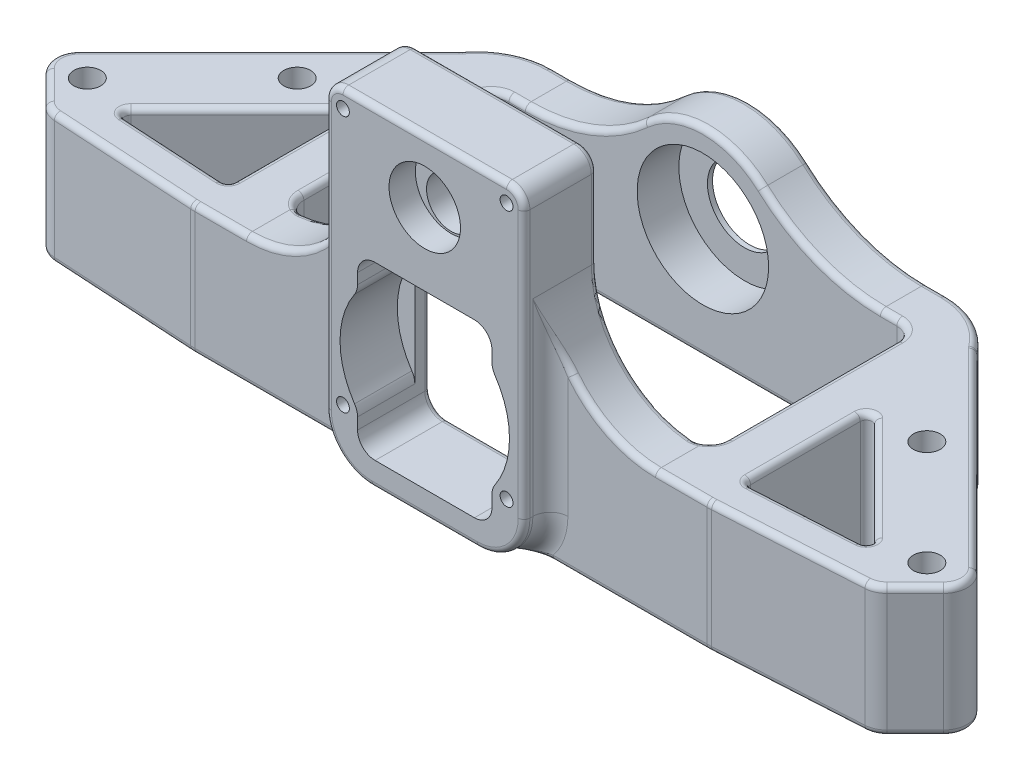
SolidWorks part; units mm, degrees
ref_plane "Front Plane" through (0, 0, 0) normal (0, 0, 1) x (1, 0, 0)
ref_plane "Top Plane" through (0, 0, 0) normal (0, 1, 0) x (1, 0, 0)
ref_plane "Right Plane" through (0, 0, 0) normal (1, 0, 0) x (0, 0, -1)
sketch "Sketch1" plane through (0, 0, 0) normal (0, 1, 0) x (1, 0, 0)
  line L0 (-44.195, -25.55) -> (-44.195, 25.55)
  line L1 (36.195, -17.55) -> (-36.195, -17.55)
  line L2 (36.195, -17.55) -> (36.195, 17.55)
  line L3 (36.195, 17.55) -> (-36.195, 17.55)
  line L4 (-36.195, -17.55) -> (-36.195, 17.55)
  line L5 (36.195, -17.55) -> (-36.195, 17.55) construction
  line L6 (36.195, 17.55) -> (-36.195, -17.55) construction
  line L11 (44.195, 25.55) -> (-44.195, 25.55)
  line L12 (44.195, -25.55) -> (44.195, 25.55)
  line L13 (44.195, -25.55) -> (-44.195, -25.55)
  line L14 (-79.6522, -15.223) -> (-70.8875, -23.9877)
  line L15 (-70.8875, -23.9877) -> (-44.195, 2.7047)
  line L16 (-79.6522, -15.223) -> (-44.195, 20.2342)
  line L17 (0, 0) -> (0, 65.6417) construction
  line L18 (-75.3776, -19.4976) -> (0, 55.88) construction
  line L19 (-44.195, -25.55) -> (-70.8875, -23.9877)
  line L20 (-44.195, -19.5397) -> (-65.2095, -18.3098)
  line L21 (44.195, -25.55) -> (70.8875, -23.9877)
  line L22 (44.195, -19.5397) -> (65.2095, -18.3098)
  line L23 (79.6522, -15.223) -> (44.195, 20.2342)
  line L24 (79.6522, -15.223) -> (70.8875, -23.9877)
  line L25 (70.8875, -23.9877) -> (44.195, 2.7047)
  line L26 (-75.3776, -19.4976) -> (-269.4077, -213.5277) construction
  circle A0 centre (-71.842, -15.962) radius 2.3
  circle A1 centre (-53.8815, 1.9985) radius 2.3
  circle A4 centre (53.8815, 1.9985) radius 2.3
  circle A5 centre (71.842, -15.962) radius 2.3
  point P0 (0, 0)
  point P21 (-75.3776, -19.4976)
  point P32 (-197.5656, -141.6856)
  point P34 (-215.5261, -159.6461)
  point P38 (0, 0)
  point P39 (0, 0)
  dimension "D10" = 4.6
  dimension "D1" = 8
  dimension "D2" = 45
  dimension "D3" = 55.88
  dimension "D4" = 5
  dimension "D5" = 76.2
  dimension "D6" = 12.3952
  dimension "D7" = 25.4
  dimension "D8" = 72.39
  dimension "D9" = 35.1
  dimension "D11" = 6
  dimension "D12" = 381
  dimension "D13" = 101.6
  dimension "D14" = 177.8
  dimension "D15" = 25.4
  dimension "D16" = 228.6
  dimension "D17" = 6.35
extrude "Boss-Extrude1" add sketch "Sketch1" along normal blind 22.25 contours L13 L12 L11 L0 L1 L4 L3 L2 | L0 L20 L15 L19 | L21 L25 L22 L12 | L25 L24 L23 L12 A4 A5 | L16 L14 L15 L0 A1 A0 region at (-56.1781, 0, 21.9627) region at (-43.174, 0, 22.5449) region at (56.1781, 0, 21.9627) region at (-59.6388, 0, 3.5495) region at (59.6388, 0, 3.5495)
extrude "Boss-Extrude2" add sketch "Sketch1<3>" along normal blind 15.85 from surface contours L13 L12 L11 L0 L1 L4 L3 L2 region at (-43.174, 0, 22.5449) starting at face at (51.1998, 22.25, 11.7149)
sketch "Sketch1<3>" plane through (0, 0, 0) normal (0, 1, 0) x (1, 0, 0) same geometry as "Sketch1"
sketch "Sketch3" plane through (0, 0, 25.55) normal (0, 0, 1) x (1, 0, 0)
  line L0 (0, 0) -> (0, 38.1) construction
  line L1 (-44.195, 38.1) -> (44.195, 38.1) construction
  line L13 (-44.195, 22.25) -> (-17, 22.25)
  line L14 (-17, 22.25) -> (-17, 56.7)
  line L15 (-17, 56.7) -> (17, 56.7)
  line L16 (17, 56.7) -> (17, 22.25)
  line L17 (17, 22.25) -> (44.195, 22.25)
  line L18 (44.195, 38.1) -> (44.195, 22.25) construction
  line L19 (44.195, 22.25) -> (44.195, 38.1)
  line L20 (44.195, 38.1) -> (17, 38.1)
  line L21 (-17, 38.1) -> (-44.195, 38.1)
  line L22 (-44.195, 38.1) -> (-44.195, 22.25)
  line L23 (-17, 38.1) -> (17, 38.1)
  line L24 (11.5, 33.65) -> (-11.5, 33.65)
  line L25 (-11.5, 33.65) -> (-11.5, 27.8818)
  line L26 (11.5, 33.65) -> (11.5, 27.8818)
  line L27 (-44.195, 22.25) -> (-70.8875, 22.25) construction
  line L28 (44.195, 0) -> (-44.195, 0) construction
  line L29 (11.5, 4.3) -> (-11.5, 4.3)
  line L30 (-11.5, 4.3) -> (-11.5, 10.2182)
  line L31 (11.5, 4.3) -> (11.5, 10.2182)
  line L32 (-11.5, 27.8818) -> (-11.5, 10.2182)
  line L33 (11.5, 27.8818) -> (11.5, 10.2182)
  circle A0 centre (14, 9.8) radius 1.1
  circle A1 centre (-14, 9.8) radius 1.1
  circle A2 centre (-14, 53.7) radius 1.1
  circle A3 centre (14, 53.7) radius 1.1
  circle A4 centre (0, 46.05) radius 6.114
  circle A20 centre (0, 44.45) radius 4.2
  circle A21 centre (0, 19.05) radius 14.5
  point P5 (0, 19.05)
  point P10 (0, 33.65)
  point P17 (0, 19.05)
  point P19 (0, 4.3)
  point P90 (-44.195, 22.25)
  line M46 (44.195, 22.25) -> (44.195, 38.1)
  line M47 (44.195, 38.1) -> (-44.195, 38.1)
  line M48 (-44.195, 38.1) -> (-44.195, 22.25)
  dimension "D1" = 2.2
  dimension "D5" = 12.228
  dimension "D6" = 8.4
  dimension "D8" = 1.6
  dimension "D14" = 34
  dimension "D15" = 29
  dimension "D2" = 3
  dimension "D3" = 3
  dimension "D4" = 3
  dimension "D7" = 25.4
  dimension "D9" = 28
  dimension "D10" = 43.9
  dimension "D11" = 34.45
  dimension "D12" = 27.195
  dimension "D13" = 19.05
  dimension "D16" = 23
  dimension "D17" = 14.6
  dimension "D18" = 14.75
extrude "Boss-Extrude3" add sketch "Sketch3" against normal up to surface (8 mm away) contours L16 L15 L14 L23 A4 A3 A2 M47 region at (-16.6124, 47.4, 25.55) up to face at (0, 19.05, 17.55)
extrude "Cut-Extrude1" cut sketch "Sketch3<3>" against normal up to next contours L13 L14 M47 M48 | L16 L17 M46 M47 region at (-30.5975, 30.175, 25.55) region at (30.5975, 30.175, 25.55)
sketch "Sketch3<3>" plane through (0, 0, 25.55) normal (0, 0, 1) x (1, 0, 0) same geometry as "Sketch3"
extrude "Cut-Extrude2" cut sketch "Sketch3<4>" against normal up to next contours L0 A21 | A21 L0 | L29 L0 A21 L30 | L0 L29 L31 A21 | L0 A21 L26 L24 | A21 L0 L24 L25 | A0 | A1 | L32 A21 | L33 A21 region at (-8.3672, 5.9503, 25.55) region at (8.3672, 5.9503, 25.55) region at (-5.3485, 19.05, 25.55) region at (5.3485, 19.05, 25.55) region at (-8.5839, 32.0193, 25.55) region at (8.5839, 32.0193, 25.55) region at (-12.7113, 19.05, 25.55) region at (12.7113, 19.05, 25.55) region at (14, 9.8, 25.55) region at (-14, 9.8, 25.55)
sketch "Sketch3<4>" plane through (0, 0, 25.55) normal (0, 0, 1) x (1, 0, 0) same geometry as "Sketch3"
sketch "Sketch4" plane through (0, 0, -25.55) normal (0, 0, -1) x (-1, 0, 0)
  line L0 (0, 0) -> (0, 38.1) construction
  line L1 (17, 38.1) -> (-17, 38.1) construction
  line L5 (-17, 22.25) -> (-14.6547, 22.25)
  line L6 (-17, 22.25) -> (-17, 38.1)
  line L7 (-17, 38.1) -> (17, 38.1)
  line L8 (17, 38.1) -> (17, 22.25)
  line L9 (17, 22.25) -> (14.6547, 22.25)
  circle A0 centre (0, 19.05) radius 6.35
  circle A1 centre (0, 19.05) radius 15
  line M7 (17, 22.25) -> (17, 38.1)
  line M8 (17, 38.1) -> (-17, 38.1)
  line M9 (-17, 38.1) -> (-17, 22.25)
  dimension "D1" = 30
  dimension "D2" = 12.7
extrude "Cut-Extrude3" cut sketch "Sketch4" against normal up to next contours A1 L0 L7 L5 M9 | L0 A1 L9 M7 M8 | L0 A0 | A0 L0 region at (2.695, 19.05, -25.55) region at (-2.695, 19.05, -25.55) region at (10.8276, 32.9317, -25.55) region at (-10.8276, 32.9317, -25.55)
extrude "Boss-Extrude6" add sketch "Sketch3<7>" along normal blind 2.7 from surface contours L32 A21 | L33 A21 region at (12.7113, 19.05, 25.55) region at (-12.7113, 19.05, 25.55) starting at face at (-12.9, 9.8, 17.55)
sketch "Sketch3<7>" plane through (0, 0, 25.55) normal (0, 0, 1) x (1, 0, 0) same geometry as "Sketch3"
sketch "Sketch9" plane through (0, 0, 25.55) normal (0, 0, 1) x (1, 0, 0)
  line L0 (-17, 22.25) -> (-17, 0)
  line L1 (17, 22.25) -> (17, 0)
  line L6 (-11.5, 33.65) -> (-11.5, 27.8818)
  line L7 (11.5, 33.65) -> (-11.5, 33.65)
  line L8 (11.5, 27.8818) -> (11.5, 33.65)
  line L9 (11.5, 4.3) -> (11.5, 10.2182)
  line L10 (-11.5, 4.3) -> (11.5, 4.3)
  line L11 (-11.5, 10.2182) -> (-11.5, 4.3)
  line L12 (-11.5, 33.65) -> (-11.5, 27.8818)
  line L13 (11.5, 33.65) -> (-11.5, 33.65)
  line L14 (11.5, 27.8818) -> (11.5, 33.65)
  line L15 (11.5, 4.3) -> (11.5, 10.2182)
  line L16 (-11.5, 4.3) -> (11.5, 4.3)
  line L17 (-11.5, 10.2182) -> (-11.5, 4.3)
  line L20 (-17, 22.25) -> (-44.195, 22.25)
  line L21 (-44.195, 22.25) -> (-44.195, 0)
  line L22 (-44.195, 0) -> (44.195, 0)
  line L23 (44.195, 0) -> (44.195, 22.25)
  line L24 (44.195, 22.25) -> (17, 22.25)
  line L25 (17, 22.25) -> (17, 56.7)
  line L26 (17, 56.7) -> (-17, 56.7)
  line L27 (-17, 56.7) -> (-17, 22.25)
  line L28 (-17, 22.25) -> (-44.195, 22.25)
  line L29 (-44.195, 22.25) -> (-44.195, 0)
  line L30 (-44.195, 0) -> (44.195, 0)
  line L31 (44.195, 0) -> (44.195, 22.25)
  line L32 (44.195, 22.25) -> (17, 22.25)
  line L33 (17, 22.25) -> (17, 56.7)
  line L34 (17, 56.7) -> (-17, 56.7)
  line L35 (-17, 56.7) -> (-17, 22.25)
  circle A1 centre (0, 46.05) radius 6.114
  circle A2 centre (0, 46.05) radius 6.114
  circle A3 centre (14, 53.7) radius 1.1
  circle A4 centre (14, 53.7) radius 1.1
  circle A5 centre (-14, 53.7) radius 1.1
  circle A6 centre (-14, 53.7) radius 1.1
  circle A7 centre (14, 9.8) radius 1.1
  circle A8 centre (14, 9.8) radius 1.1
  circle A9 centre (-14, 9.8) radius 1.1
  arc A10 (11.5, 10.2182) -> (11.5, 27.8818) centre (0, 19.05) ccw
  arc A11 (-11.5, 27.8818) -> (-11.5, 10.2182) centre (0, 19.05) ccw
  arc A12 (11.5, 10.2182) -> (11.5, 27.8818) centre (0, 19.05) ccw
  arc A13 (-11.5, 27.8818) -> (-11.5, 10.2182) centre (0, 19.05) ccw
  circle A14 centre (-14, 9.8) radius 1.1
  circle M22 centre (-14, 9.8) radius 1.1
  line M23 (-11.5, 27.8818) -> (-11.5, 33.65)
  line M24 (-11.5, 33.65) -> (11.5, 33.65)
  line M25 (11.5, 33.65) -> (11.5, 27.8818)
  arc M26 (11.5, 27.8818) -> (11.5, 10.2182) centre (0, 19.05) cw
  line M27 (11.5, 10.2182) -> (11.5, 4.3)
  line M28 (11.5, 4.3) -> (-11.5, 4.3)
  line M29 (-11.5, 4.3) -> (-11.5, 10.2182)
  arc M30 (-11.5, 10.2182) -> (-11.5, 27.8818) centre (0, 19.05) cw
  circle M31 centre (14, 9.8) radius 1.1
  line M34 (-44.195, 0) -> (44.195, 0)
  line M37 (17, 22.25) -> (17, 56.7)
  line M38 (17, 56.7) -> (-17, 56.7)
  line M39 (-17, 56.7) -> (-17, 22.25)
  circle M40 centre (0, 46.05) radius 6.114
  circle M41 centre (14, 53.7) radius 1.1
  circle M42 centre (-14, 53.7) radius 1.1
  dimension "D1" = 0
  dimension "D2" = 0
  dimension "D3" = 0
  dimension "D4" = 0
  dimension "D5" = 0
  dimension "D6" = 0
  dimension "D7" = 0
extrude "Boss-Extrude7" add sketch "Sketch9" along normal blind 4.5 contours L1 L0 M37 M38 M39 M34 M30 M23 M24 M25 M26 M27 M28 M29 M31 M40 M42 M41 M22 region at (-16.3389, 39.475, 25.55)
fillet "Fillet1" radius 18 2 edges at (17, 22.25, 21.55) (-17, 22.25, 21.55)
fillet "Fillet2" radius 3 2 edges at (-17, 56.7, 23.8) (17, 56.7, 23.8)
fillet "Fillet4" radius 1 6 edges at (65.2095, 11.125, 18.3098) (44.195, 11.125, 19.5397) (44.195, 11.125, -2.7047) (-44.195, 11.125, -2.7047) (-44.195, 11.125, 19.5397) (-65.2095, 11.125, 18.3098)
fillet "Fillet5" radius 3 4 edges at (-36.195, 11.125, -17.55) (36.195, 11.125, -17.55) (36.195, 11.125, 17.55) (-36.195, 11.125, 17.55)
fillet "Fillet6" radius 13 4 edges at (44.195, 11.125, -25.55) (-44.195, 11.125, -25.55) (-44.195, 11.125, 25.55) (44.195, 11.125, 25.55)
fillet "Fillet7" radius 4 4 edges at (79.6522, 11.125, 15.223) (70.8875, 11.125, 23.9877) (-70.8875, 11.125, 23.9877) (-79.6522, 11.125, 15.223)
fillet "Fillet12" radius 8 2 edges at (-17, 0, 27.8) (17, 0, 27.8)
sketch "Sketch5" plane through (0, 0, -17.55) normal (0, 0, 1) x (1, 0, 0)
  circle A0 centre (0, 19.05) radius 11.25
  dimension "D1" = 22.5
extrude "Cut-Extrude4" cut sketch "Sketch5" against normal blind 7.1374
fillet "Fillet16" radius 3 4 edges at (14.6569, 2.3431, 25.55) (-14.6569, 2.3431, 25.55) (17, 24.125, 25.55) (-17, 24.125, 25.55)
fillet "Fillet8" radius 30 2 edges at (14.6547, 22.25, -21.55) (-14.6547, 22.25, -21.55)
fillet "Fillet10" radius 2 2 edges at (-44.195, 11.125, -20.2342) (44.195, 11.125, -20.2342)
fillet "Fillet9" radius 1 108 edges at (-34.1764, 22.2689, 17.3849) (-35.8797, 22.25, 15.8888) (-36.195, 22.25, 0) (-35.3163, 22.25, -16.6713) (-31.786, 22.25, -17.55) (-19.5142, 24.2857, -17.55) (0, 34.05, -17.55) (19.5142, 24.2857, -17.55) (31.786, 22.25, -17.55) (35.3163, 22.25, -16.6713) (36.195, 22.25, 0) (35.8797, 22.25, 15.8888) (34.1145, 22.2718, 17.4056) (21.6492, 28.1771, 17.55) (17, 46.975, 17.55) (16.1213, 55.8213, 17.55) (0, 56.7, 17.55) (-16.1213, 55.8213, 17.55) (-17, 46.975, 17.55) (-32.0431, 22.25, -25.55) (-19.5142, 24.2857, -25.55) (0, 34.05, -25.55) (19.5142, 24.2857, -25.55) (32.0431, 22.25, -25.55) (44.195, 22.25, 9.0945) (26.4882, 24.3897, 25.55) (-26.4882, 24.3897, 25.55) (-44.195, 22.25, 9.0945) (-35.3163, 0, 16.6713) (0, 0, 17.55) (35.3163, 0, 16.6713) (36.195, 0, 0) (35.3163, 0, -16.6713) (0, 0, -17.55) (-35.3163, 0, -16.6713) (44.195, 0, 9.0945) (-44.195, 0, 9.0945) (-21.6492, 28.1771, 17.55) (-36.195, 0, 0) (0, 0, -25.55) (39.4074, 22.25, 25.55) (-39.4074, 22.25, 25.55) (-44.5089, 0, 19.207) (-54.1195, 0, 18.9589) (-63.8618, 0, 17.7972) (-54.7682, 0, 7.8684) (-44.8123, 0, -1.2144) (-44.8123, 22.25, -1.2144) (-54.7682, 22.25, 7.8684) (-63.8618, 22.25, 17.7972) (-54.1195, 22.25, 18.9589) (-44.5089, 22.25, 19.207) (39.5259, 0, -24.1761) (-39.5259, 0, -24.1761) (63.8618, 22.25, 17.7972) (54.1195, 22.25, 18.9589) (44.5089, 22.25, 19.207) (44.8123, 22.25, -1.2144) (44.5089, 0, 19.207) (54.1195, 0, 18.9589) (63.8618, 0, 17.7972) (54.7682, 0, 7.8684) (44.8123, 0, -1.2144) (-60.5616, 0, -3.8676) (-77.9953, 0, 15.223) (60.5616, 0, -3.8676) (77.9953, 0, 15.223) (74.3935, 0, 20.4816) (70.773, 0, 23.7326) (56.9715, 0, 24.8022) (44.1948, 0, 25.5444) (-44.1948, 0, 25.5444) (-56.9715, 0, 24.8022) (-70.773, 0, 23.7326) (-60.5616, 22.25, -3.8676) (-77.9953, 22.25, 15.223) (60.5616, 22.25, -3.8676) (77.9953, 22.25, 15.223) (74.3935, 22.25, 20.4816) (70.773, 22.25, 23.7326) (56.9715, 22.25, 24.8022) (44.1948, 22.25, 25.5444) (-44.1948, 22.25, 25.5444) (-56.9715, 22.25, 24.8022) (-70.773, 22.25, 23.7326) (54.7682, 22.25, 7.8684) (-74.3935, 0, 20.4816) (-74.3935, 22.25, 20.4816) (-44.2025, 0, -20.2339) (44.2025, 0, -20.2339) (-44.2025, 22.25, -20.2339) (-39.5259, 22.25, -24.1761) (39.5259, 22.25, -24.1761) (44.2025, 22.25, -20.2339) (30.1824, 0, 25.55) (-30.1824, 0, 25.55) (16.1213, 55.8213, 30.05) (0, 56.7, 30.05) (-16.1213, 55.8213, 30.05) (-17, 30.85, 30.05) (-14.6569, 2.3431, 30.05) (0, 0, 30.05) (14.6569, 2.3431, 30.05) (17, 30.85, 30.05) (14.0902, 0, 25.9624) (-14.0902, 0, 25.9624) (18.5515, 32.9393, 25.9229) (-18.5515, 32.9393, 25.9229)
fillet "Fillet11" radius 3 8 edges at (-11.5, 4.3, 23.8) (11.5, 4.3, 23.8) (11.5, 33.65, 23.8) (-11.5, 33.65, 23.8) (11.5, 27.8818, 25.15) (11.5, 10.2182, 25.15) (-11.5, 27.8818, 25.15) (-11.5, 10.2182, 25.15)
fillet "Fillet14" radius 1 8 edges at (-10.6213, 5.1787, 17.55) (-11.5, 18.975, 17.55) (-10.6213, 32.7713, 17.55) (0, 33.65, 17.55) (10.6213, 32.7713, 17.55) (11.5, 18.975, 17.55) (10.6213, 5.1787, 17.55) (0, 4.3, 17.55)
extrude "Boss-Extrude8" add sketch "Sketch3<8>" against normal up to surface (8 mm away) contours A4 A20 region at (-5.9411, 46.05, 25.55) up to face at (0, 18.975, 17.55)
sketch "Sketch3<8>" plane through (0, 0, 25.55) normal (0, 0, 1) x (1, 0, 0) same geometry as "Sketch3"
